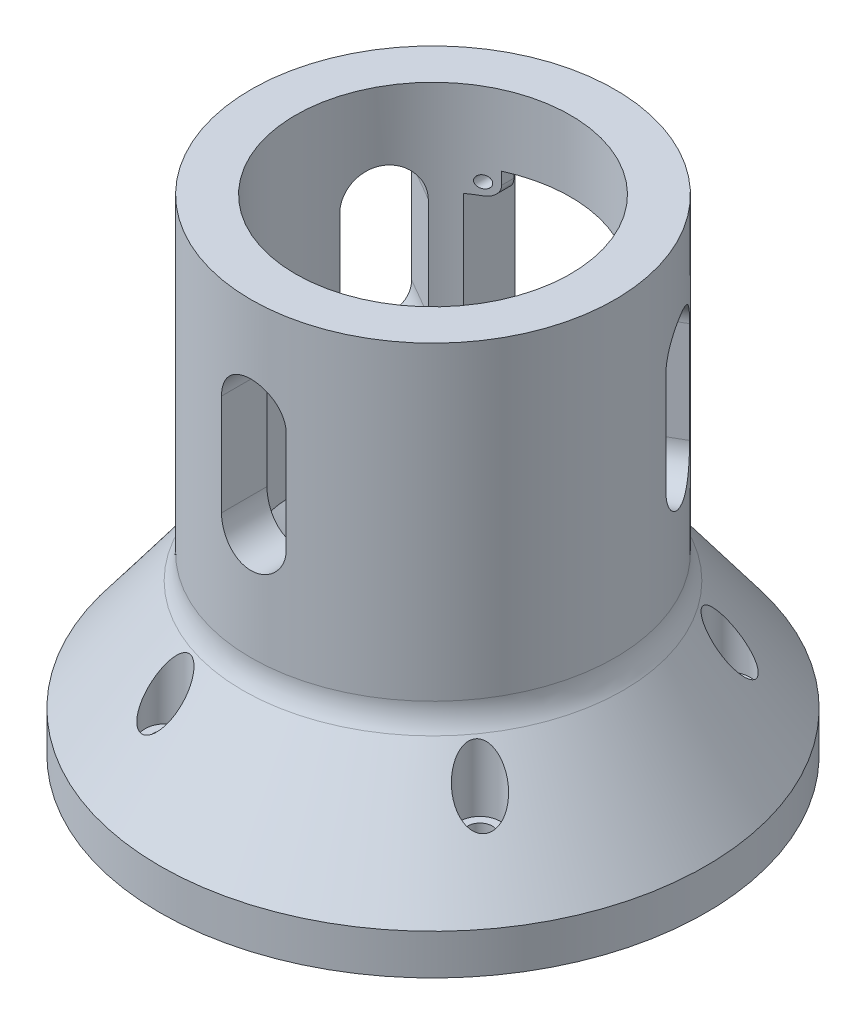
SolidWorks part; units mm, degrees
ref_plane "Front Plane" through (0, 0, 0) normal (0, 0, 1) x (1, 0, 0)
ref_plane "Top Plane" through (0, 0, 0) normal (0, 1, 0) x (1, 0, 0)
ref_plane "Right Plane" through (0, 0, 0) normal (1, 0, 0) x (0, 0, -1)
sketch "Sketch1" plane through (0, 0, 0) normal (0, 1, 0) x (1, 0, 0)
  circle A0 centre (0, 0) radius 67.5
  dimension "D1" = 135
ref_plane "Plane1" through (0, 30, 0) normal (0, 1, 0) x (1, 0, 0)
sketch "Sketch2" plane through (0, 30, 0) normal (0, 1, 0) x (1, 0, 0)
  circle A0 centre (0, 0) radius 45
  dimension "D1" = 90
loft "Loft1" add profiles "Sketch1", "Sketch2" connector at (0, 0, 67.5) connector at (0, 30, 45)
sketch "Sketch4" plane through (0, 30, 0) normal (0, 1, 0) x (1, 0, 0)
  circle A0 centre (0, 0) radius 52.5 construction
  circle A1 centre (-52.5, 0) radius 3
  circle A2 centre (-16.2234, 49.9305) radius 3
  circle A3 centre (42.4734, 30.8587) radius 3
  circle A4 centre (42.4734, -30.8587) radius 3
  circle A5 centre (-16.2234, -49.9305) radius 3
  point P15 (0, 0)
  dimension "D1" = 105
  dimension "D2" = 6
  dimension "D3" = 5
extrude "Cut-Extrude2" cut sketch "Sketch4" against normal through all
sketch "Sketch5" plane through (0, 30, 0) normal (0, 1, 0) x (1, 0, 0)
  circle A0 centre (-52.5, 0) radius 3 construction
  circle A1 centre (-52.5, 0) radius 3
  circle A2 centre (-52.5, 0) radius 5
  circle A3 centre (-16.2234, 49.9305) radius 5
  circle A4 centre (42.4734, 30.8587) radius 5
  circle A5 centre (42.4734, -30.8587) radius 5
  circle A6 centre (-16.2234, -49.9305) radius 5
  point P14 (0, 0)
  dimension "D1" = 10
  dimension "D3" = 52.5
  dimension "D2" = 5
extrude "Cut-Extrude3" cut sketch "Sketch5" against normal blind 20
sketch "Sketch6" plane through (0, 30, 0) normal (0, 1, 0) x (1, 0, 0)
  circle A1 centre (0, 0) radius 45
  circle A2 centre (0, 0) radius 45
  dimension "D1" = 0
extrude "Boss-Extrude1" add sketch "Sketch6" along normal blind 80
fillet "Fillet1" radius 10 1 edges at (0, 30, 45)
sketch "Sketch11" plane through (17.444, 57.5446, 0) normal (0, 0, 1) x (1, 0, 0)
  line L0 (-17.444, 52.4554) -> (-51.444, 52.4554)
  line L1 (27.556, 52.4554) -> (-62.444, 52.4554) construction
  line L2 (-51.444, 52.4554) -> (-51.444, -28.5446)
  line L5 (-51.444, -28.5446) -> (-40.444, -38.7852)
  line L8 (-40.444, -38.7852) -> (-17.444, -38.7852)
  line L9 (-17.444, 52.4554) -> (-17.444, -38.7852)
  dimension "D1" = 34
  dimension "D2" = 137.047
  dimension "D3" = 23
  dimension "D4" = 81
revolve "Cut-Revolve1" cut sketch "Sketch11" angle 360 about L9
sketch "Sketch12" plane through (0, 0, 0) normal (0, -1, 0) x (1, 0, 0)
  circle A1 centre (0, 0) radius 67.5
  circle A2 centre (0, 0) radius 67.5
  dimension "D1" = 0
extrude "Boss-Extrude2" add sketch "Sketch12" along normal blind 10
sketch "Sketch15" plane through (0, -10, 0) normal (0, -1, 0) x (1, 0, 0)
  circle A0 centre (42.4734, 30.8587) radius 3 construction
  circle A3 centre (-52.5, 0) radius 3
  circle A4 centre (-52.5, 0) radius 3
  circle A5 centre (42.4734, -30.8587) radius 3 construction
  circle A6 centre (-16.2234, -49.9305) radius 3 construction
  circle A7 centre (-16.2234, 49.9305) radius 3 construction
  circle A8 centre (42.4734, 30.8587) radius 3
  circle A9 centre (42.4734, -30.8587) radius 3
  circle A10 centre (-16.2234, -49.9305) radius 3
  circle A11 centre (-16.2234, 49.9305) radius 3
  point P18 (0, 0)
  dimension "D2" = 0
extrude "Cut-Extrude5" cut sketch "Sketch15" against normal blind 20
sketch "Sketch16" plane through (0, 0, 0) normal (0, 0, 1) x (1, 0, 0)
  line L0 (0, 85) -> (0, 60) construction
  line L1 (8, 85) -> (8, 60)
  line L2 (-8, 85) -> (-8, 60)
  arc A0 (8, 85) -> (-8, 85) centre (0, 85) ccw
  arc A1 (-8, 60) -> (8, 60) centre (0, 60) ccw
  point P3 (0, 72.5)
  point P8 (0, 0)
  dimension "D3" = 8
  dimension "D1" = 60
  dimension "D2" = 25
extrude "Cut-Extrude6" cut sketch "Sketch16" along normal blind 50
pattern_circular "CirPattern1" count 3 every 120 about axis through (0, 110, 0) along (0, 1, 0) of "Cut-Extrude6"
sketch "Sketch18" plane through (0, 0, 0) normal (0, 0, 1) x (1, 0, 0)
  line L0 (0, 0) -> (0, 72.5) construction
  line L1 (17, 86.5) -> (20, 86.5)
  line L2 (14, 92.5) -> (-14, 92.5)
  line L3 (20, 86.5) -> (20, 58.5)
  line L4 (14, 52.5) -> (-14, 52.5)
  line L5 (-20, 86.5) -> (-20, 58.5)
  line L6 (14.8787, 87.3787) -> (-14.8787, 57.6213) construction
  line L8 (14, 89.5) -> (14, 92.5)
  line L9 (14, 55.5) -> (14, 52.5)
  line L10 (17, 58.5) -> (20, 58.5)
  line L11 (-17, 58.5) -> (-20, 58.5)
  line L12 (-14, 55.5) -> (-14, 52.5)
  line L13 (-14, 89.5) -> (-14, 92.5)
  line L14 (-17, 86.5) -> (-20, 86.5)
  line L17 (14.8787, 57.6213) -> (-14.8787, 87.3787) construction
  arc A5 (14, 89.5) -> (17, 86.5) centre (17, 89.5) ccw
  arc A6 (17, 58.5) -> (14, 55.5) centre (17, 55.5) ccw
  arc A7 (-14, 55.5) -> (-17, 58.5) centre (-17, 55.5) ccw
  arc A8 (-17, 86.5) -> (-14, 89.5) centre (-17, 89.5) ccw
  point P39 (0, 72.5)
  dimension "D1" = 72.5
  dimension "D2" = 4
extrude "Cut-Extrude7" cut sketch "Sketch18" against normal blind 50
ref_plane "Plane2" through (0, 0, -60) normal (0, 0, 1) x (1, 0, 0)
sketch "Sketch22" plane through (0, 0, -60) normal (0, 0, 1) x (1, 0, 0)
  line L0 (0, 0) -> (0, 72.5) construction
  line L1 (-67.5, 0) -> (67.5, 0) construction
  line L3 (20, 92.5) -> (-20, 92.5)
  line L4 (20, 92.5) -> (20, 52.5)
  line L5 (20, 52.5) -> (-20, 52.5)
  line L6 (-20, 92.5) -> (-20, 52.5)
  line L7 (20, 92.5) -> (-20, 52.5) construction
  line L8 (20, 52.5) -> (-20, 92.5) construction
  dimension "D1" = 72.5
  dimension "D2" = 40
  dimension "D3" = 40
extrude "Cut-Extrude8" cut sketch "Sketch22" along normal blind 26
sketch "Sketch23" plane through (0, 0, -60) normal (0, 0, 1) x (1, 0, 0)
  line L0 (0, 0) -> (0, 72.5) construction
  line L1 (0, 72.5) -> (-5.5729, 72.5) construction
  line L2 (20, 92.5) -> (-20, 92.5) construction
  line L3 (20, 92.5) -> (20, 52.5) construction
  line L4 (20, 52.5) -> (-20, 52.5) construction
  line L5 (-20, 92.5) -> (-20, 52.5) construction
  line L6 (20, 92.5) -> (-20, 52.5) construction
  line L7 (20, 52.5) -> (-20, 92.5) construction
  circle A0 centre (17, 89.5) radius 1.5
  circle A1 centre (-17, 89.5) radius 1.5
  circle A2 centre (-17, 55.5) radius 1.5
  circle A3 centre (17, 55.5) radius 1.5
  dimension "D3" = 3
  dimension "D5" = 3
  dimension "D1" = 72.5
  dimension "D2" = 40
  dimension "D4" = 17
  dimension "D6" = 17
extrude "Cut-Extrude9" cut sketch "Sketch23" along normal blind 36
